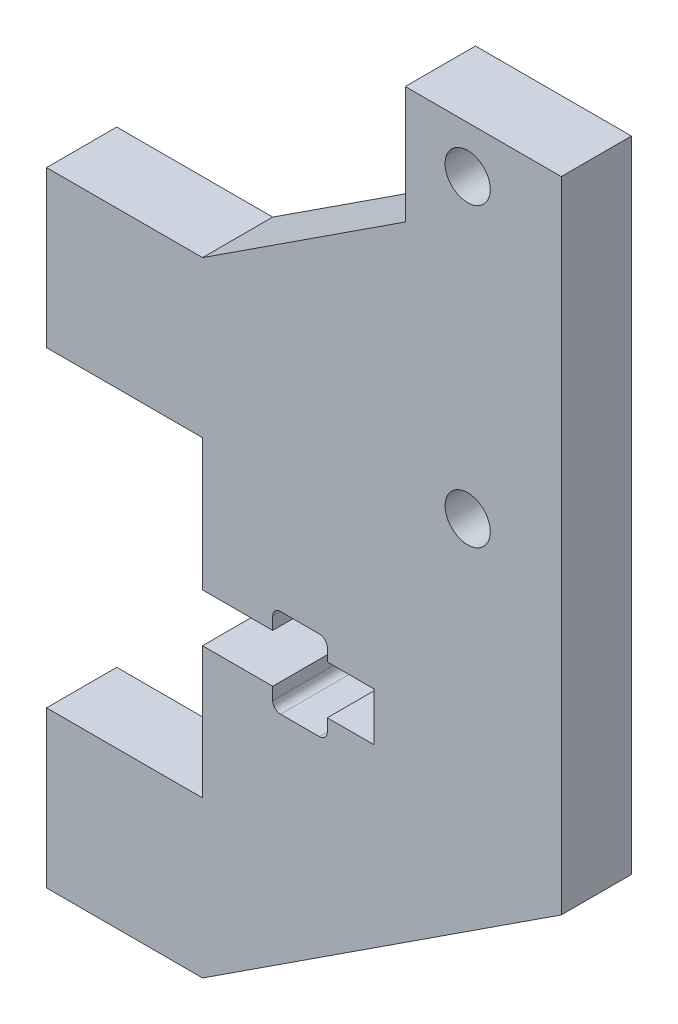
SolidWorks part; units mm, degrees
ref_plane "Front Plane" through (0, 0, 0) normal (0, 0, 1) x (1, 0, 0)
ref_plane "Top Plane" through (0, 0, 0) normal (0, 1, 0) x (1, 0, 0)
ref_plane "Right Plane" through (0, 0, 0) normal (1, 0, 0) x (0, 0, -1)
sketch "Sketch1" plane through (0, 0, 0) normal (0, 0, 1) x (1, 0, 0)
  line L0 (13, 3.4783) -> (0, -5)
  line L1 (0, -5) -> (-10, -5)
  line L2 (-10, -5) -> (-10, -15)
  line L3 (-10, -15) -> (0, -15)
  line L4 (0, -15) -> (0, -35)
  line L5 (0, -35) -> (-10, -35)
  line L6 (-10, -35) -> (-10, -45)
  line L7 (-10, -45) -> (0, -45)
  line L10 (0, -45) -> (23, -30)
  line L11 (23, -30) -> (23, 11)
  line L12 (23, 11) -> (13, 11)
  line L13 (13, 11) -> (13, 3.4783)
  line L15 (0, -5) -> (0, -45) construction
  line L16 (-10, -10) -> (0, -10) construction
  line L17 (-10, -40) -> (0, -40) construction
  line L18 (-10, -15) -> (-10, -35) construction
  line L19 (-10, -25) -> (0, -25) construction
  dimension "D1" = 10
  dimension "D2" = 10
  dimension "D3" = 10
  dimension "D4" = 10
  dimension "D5" = 15
  dimension "D8" = 10
  dimension "D10" = 13
  dimension "D6" = 15
  dimension "D7" = 16
extrude "Boss-Extrude1" add sketch "Sketch1" along normal blind 4.5
sketch "Sketch2" plane through (0, 0, 4.5) normal (0, 0, 1) x (1, 0, 0)
  line L0 (0, -25) -> (23, -25) construction
  line L1 (0, -15) -> (0, -35) construction
  line L3 (11, -26.55) -> (11, -23.45) construction
  line L4 (11, -23.45) -> (0, -23.45) construction
  line L5 (0, -26.55) -> (0, -23.45)
  line L6 (0, -23.45) -> (4.5, -23.45)
  line L7 (4.5, -23.45) -> (4.5, -22.65)
  line L8 (5, -22.15) -> (7.5, -22.15)
  line L9 (8, -22.65) -> (8, -23.45)
  line L10 (8, -23.45) -> (11, -23.45)
  line L11 (11, -23.45) -> (11, -26.55)
  line L12 (11, -26.55) -> (0, -26.55) construction
  line L13 (8, -26.55) -> (11, -26.55)
  line L14 (8, -27.35) -> (8, -26.55)
  line L15 (5, -27.85) -> (7.5, -27.85)
  line L16 (4.5, -26.55) -> (4.5, -27.35)
  line L17 (0, -26.55) -> (4.5, -26.55)
  line L18 (23, -30) -> (23, 11) construction
  arc A0 (7.5, -22.15) -> (8, -22.65) centre (7.5, -22.65) cw
  arc A1 (4.5, -22.65) -> (5, -22.15) centre (5, -22.65) cw
  arc A2 (4.5, -27.35) -> (5, -27.85) centre (5, -27.35) ccw
  arc A3 (7.5, -27.85) -> (8, -27.35) centre (7.5, -27.35) ccw
  point P15 (8, -22.15)
  point P18 (4.5, -22.15)
  point P27 (11, -25)
  point P29 (4.5, -27.85)
  point P30 (8, -27.85)
  dimension "D6" = 0.5
  dimension "D1" = 11
  dimension "D2" = 1.55
  dimension "D3" = 8
  dimension "D4" = 3.5
  dimension "D5" = 2.85
extrude "screw-cutout" cut sketch "Sketch2" against normal through all
sketch "Sketch3" plane through (0, 0, 4.5) normal (0, 0, 1) x (1, 0, 0)
  line L0 (17, 55) -> (17, -45) construction
  line L3 (13, 11) -> (13, 3.4783) construction
  line L5 (-10, -45) -> (0, -45) construction
  line L10 (11, -26.55) -> (11, -23.45) construction
  circle A1 centre (17, 8) radius 1.45
  circle A5 centre (17, -11) radius 1.45
  point P8 (11, -25)
  dimension "D4" = 2.9
  dimension "D11" = 2.9
  dimension "D6" = 4
  dimension "D12" = 19
  dimension "D2" = 14
extrude "Cut-Extrude2" cut sketch "Sketch3" against normal through all
sketch "Sketch4" [suppressed] plane through (0, 0, 4.5) normal (0, 0, 1) x (1, 0, 0)
  line L0 (17, -11) -> (17, 8) construction
  line L1 (17, -1.5) -> (13, -1.5) construction
  line L2 (13, 11) -> (13, 3.4783) construction
  line L4 (15, 2.5) -> (13, 2.5)
  line L5 (15, 2.5) -> (15, -5.5)
  line L6 (15, -5.5) -> (13, -5.5)
  line L7 (13, 2.5) -> (13, -5.5)
  line L8 (15, 2.5) -> (13, -5.5) construction
  line L9 (15, -5.5) -> (13, 2.5) construction
  circle A1 centre (17, 8) radius 1.55 construction
  circle A3 centre (17, -11) radius 1.55 construction
  point P11 (14, -1.5)
  dimension "D1" = 8
  dimension "D2" = 2
  dimension "D3" = 3
equation "\"X-ROD-SPACING\"=45"
equation "\"Y-ROD-SPACING\"=75"
equation "\"Z-ROD-SPACING\"=17.5"
equation "\"Y-BED-OFFSET\"=2"
equation "\"Y-BED-ROD-INSET\"=3.5"
equation "\"T-SLOT-NUT-FILLET-RADIUS\"=0.5"
equation "\"T-SLOT-SCREW-SHAFT-RADIUS\"=1.55"
equation "\"T-SLOT-SCREW-SHAFT-CUTOUT-LENGTH\"=11.0"
equation "\"T-SLOT-NUT-DEPTH\"=3.5"
equation "\"T-SLOT-NUT-WIDTH\"=2.85"
equation "\"T-SLOT-NUT-END-DISTANCE\"=8"
equation "\"ACRYLIC-THICKNESS\"=10"
equation "\"ACRYLIC-THICKNESS2\"=4.5"
equation "\"ACRYLIC-TAB-CUTOUT-SIZE\"=\"ACRYLIC-THICKNESS\"+\"ACRYLIC-TAB-TOLERANCE\"*2"
equation "\"ACRYLIC-TAB-WIDTH\"=\"ACRYLIC-THICKNESS\""
equation "\"ACRYLIC-M3-HOLE\"=2.9"
equation "\"SMOOTHROD-CAP-SCREW-DISTANCE\"=20"
equation "\"FRAME-WIDTH-INNER\"=370"
equation "\"NEMA17-HOLE-SPACING\"=31"
equation "\"NEMA17-CENTRAL-CUTOUT\"=22.5"
equation "\"Z-BRACKET-REACH\"=55"
equation "\"Z-ROD-INSET\"=16"
equation "\"TOP-BRACKET-SPACING\"=40"
equation "\"SMOOTHROD-X-LENGTH\"=350"
equation "\"SMOOTHROD-Y-LENGTH\"=350"
equation "\"SMOOTHROD-Z-LENGTH\"=350"
equation "\"SMOOTHROD-TIGHTENING-HEADROOM\"=.25"
equation "\"LEADSCREW-Z-LENGTH\"=300"
equation "\"SCREW-LENGTH-FRAME\"=\"ACRYLIC-THICKNESS\" + 10"
equation "\"SCREW-HEAD-RADIUS\"=6"
equation "\"PRINTED-X-SMOOTHROD-DIAMETER\"=9.0"
equation "\"PRINTED-X-SMOOTHROD-CUTOUT\"=10"
equation "\"PRINTED-X-BASE-HEIGHT\"=10"
equation "\"PRINTED-LM8UU-CUTOUT-SIZE\"=15.5"
equation "\"PRINTED-LM8UU-CUTOUT-LENGTH\"=24.5"
equation "\"PRINTED-X-IDLER-HEIGHT\"=16"
equation "\"PSU-MOUNTING-WIDTH\"=95"
equation "\"PSU-MOUNTING-HEIGHT\"=177"
equation "\"Y-BELT-TO-ROD-DISTANCE\"=20"
equation "\"SPOOL-HOLDER-ROD-SPACING\"=150"
equation "\"D1@Sketch1\"=\"ACRYLIC-TAB-WIDTH\""
equation "\"D2@Sketch1\"=\"ACRYLIC-TAB-WIDTH\""
equation "\"D3@Sketch1\"=\"ACRYLIC-THICKNESS\""
equation "\"D4@Sketch1\"=\"ACRYLIC-THICKNESS\""
equation "\"D1@Boss-Extrude1\"=\"ACRYLIC-THICKNESS2\""
equation "\"D1@Sketch2\"=\"T-SLOT-SCREW-SHAFT-CUTOUT-LENGTH\""
equation "\"D2@Sketch2\"=\"T-SLOT-SCREW-SHAFT-RADIUS\""
equation "\"D3@Sketch2\"=\"T-SLOT-NUT-END-DISTANCE\""
equation "\"D4@Sketch2\"=\"T-SLOT-NUT-DEPTH\""
equation "\"D5@Sketch2\"=\"T-SLOT-NUT-WIDTH\""
equation "\"D6@Sketch2\"=\"T-SLOT-NUT-FILLET-RADIUS\""
equation "\"D4@Sketch3\"=\"ACRYLIC-M3-HOLE\""
equation "\"D11@Sketch3\"=\"ACRYLIC-M3-HOLE\""
equation "\"Y-BED-SCREW-SPACING\"=209"
equation "\"Y-BED-SCREW-CUTOUT-SLOT-HEIGHT\"=2"
equation "\"ACRYLIC-TAB-TOLERANCE\"=-.05"
equation "\"SCREW-LENGTH-MOTOR\"=\"ACRYLIC-THICKNESS\" + 5"
equation "\"SCREW-LENGTH-EXTRUDER\"=28"
equation "\"PRINTED-M3-HOLE\"=3.5"
equation "\"ACRYLIC-X-CARRIAGE-WIDTH\"=55"
equation "\"ACRYLIC-X-CARRIAGE-HEIGHT\"=75"
equation "\"ACRYLIC-X-CARRIAGE-LM8UU-CUTOUT-WIDTH\"=24.25"
equation "\"ACRYLIC-X-CARRIAGE-LM8UU-CUTOUT-HEIGHT\"=11.0"
equation "\"ACRYLIC-X-CARRIAGE-SCREW-SPACING-X\"=15"
equation "\"ACRYLIC-X-CARRIAGE-SCREW-SPACING-Y\"=33"
equation "\"ACRYLIC-X-CARRIAGE-CENTER-TAB-SPACING\"=14"
equation "\"ACRYLIC-X-CARRIAGE-EXTRUDER-OFFSET\"=26"
equation "\"ACRYLIC-X-CARRIAGE-EXTRUDER-ANGLE\"=90"
equation "\"ACRYLIC-X-CARRIAGE-EXTRUDER-SHELF-DEPTH\"=\"ACRYLIC-X-CARRIAGE-EXTRUDER-OFFSET\" + 28"
equation "\"ACRYLIC-X-CARRIAGE-EXTRUDER-BRACE-SPACING\"=23"
equation "\"ACRYLIC-X-CARRIAGE-EXTRUDER-BRACE-TAB-OFFSET\"=20"
equation "\"ACRYLIC-X-CARRIAGE-EXTRUDER-BRACE-HEIGHT\"=35"
equation "\"ACRYLIC-X-CARRIAGE-EXTRUDER-BRACE-SCREW-SPACING\"=22"
equation "\"ACRYLIC-X-CARRIAGE-DUAL-WIDTH-MULTIPLIER\"=1.65"
equation "\"ACRYLIC-X-CARRIAGE-DUAL-HOTEND-SPACING\"=42"
equation "\"ACRYLIC-X-CARRIAGE-DUAL-WIDTH\"=75"
equation "\"ACRYLIC-X-CARRIAGE-DUAL-HOTEND-SEPARATION\"=36"
equation "\"ACRYLIC-X-CARRIAGE-DUAL-MOUNT-PLATE-DEPTH\"=75"
equation "\"ACRYLIC-X-CARRIAGE-DUAL-MOUNT-BRACE-WIDTH\"=33"
equation "\"ACRYLIC-X-CARRIAGE-DUAL-MOUNT-SCREW-WIDTH\"=40"
equation "\"BLOWER-FAN-WIDTH\"=15"
